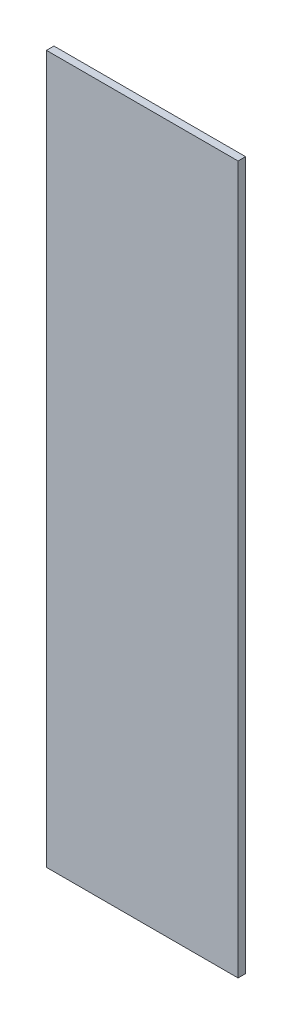
SolidWorks part; units mm, degrees
material "6061-T6 (SS)"
ref_plane "Front Plane" through (0, 0, 0) normal (0, 0, 1) x (1, 0, 0)
ref_plane "Top Plane" through (0, 0, 0) normal (0, 1, 0) x (1, 0, 0)
ref_plane "Right Plane" through (0, 0, 0) normal (1, 0, 0) x (0, 0, -1)
sketch "Sketch1" plane through (0, 0, 0) normal (0, 0, 1) x (1, 0, 0)
  line L1 (-325, 1200) -> (325, 1200)
  line L2 (-325, 1200) -> (-325, -1200)
  line L3 (-325, -1200) -> (325, -1200)
  line L4 (325, 1200) -> (325, -1200)
  line L5 (-325, 1200) -> (325, -1200) construction
  line L6 (-325, -1200) -> (325, 1200) construction
  point P1 (0, 0)
  point P6 (0, 0)
  dimension "D1" = 650
  dimension "D2" = 2400
extrude "Boss-Extrude1" add sketch "Sketch1" along normal blind 12.7 and the other way blind 12.7
